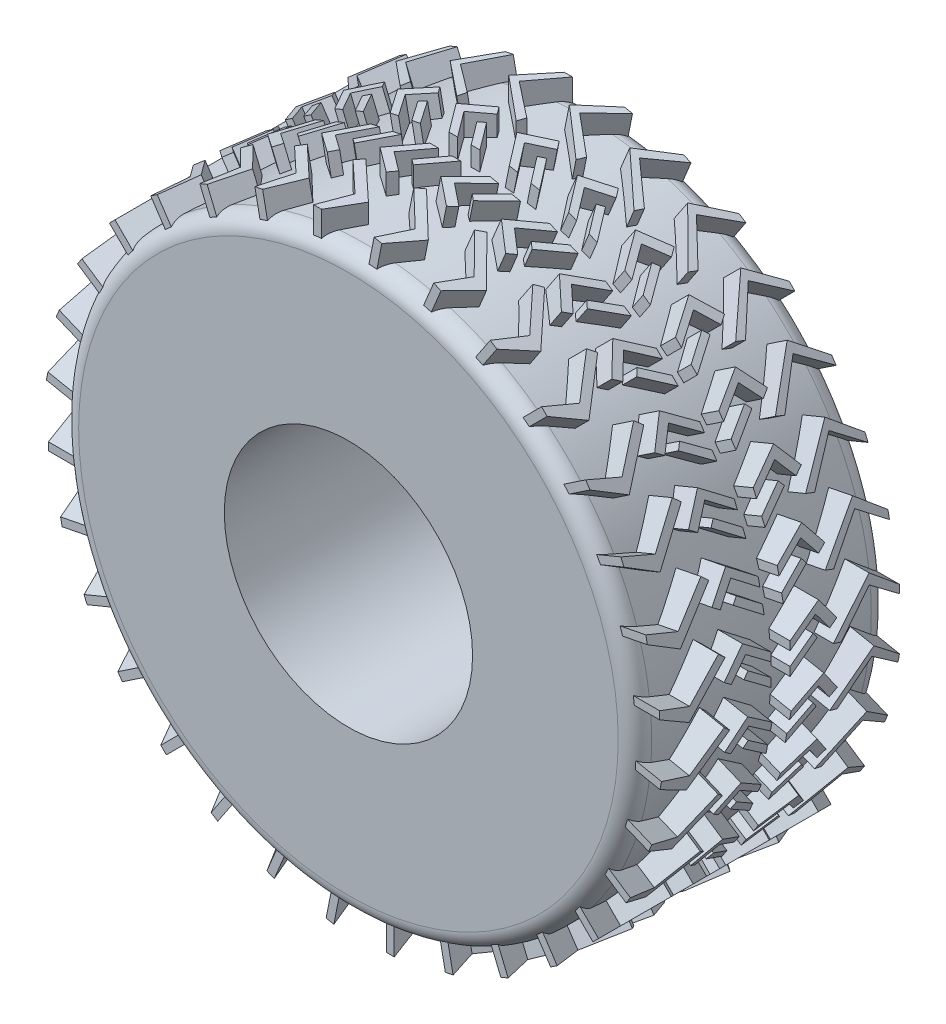
SolidWorks part; units mm, degrees
ref_plane "Front Plane" through (0, 0, 0) normal (0, 0, 1) x (1, 0, 0)
ref_plane "Top Plane" through (0, 0, 0) normal (0, 1, 0) x (1, 0, 0)
ref_plane "Right Plane" through (0, 0, 0) normal (1, 0, 0) x (0, 0, -1)
sketch "Sketch1" plane through (0, 0, 0) normal (0, 0, 1) x (1, 0, 0)
  circle A0 centre (0, 0) radius 60
  circle A1 centre (0, 0) radius 26
  dimension "D1" = 120
  dimension "D2" = 52
extrude "Boss-Extrude2" add sketch "Sketch1" along normal mid plane 53
fillet "Fillet2" radius 3.5 2 edges at (60, 0, -26.5) (60, 0, 26.5)
ref_plane "Plane1" through (0, 64, 0) normal (0, 1, 0) x (1, 0, 0)
sketch "Sketch2" plane through (0, 64, 0) normal (0, 1, 0) x (1, 0, 0)
  line L0 (0, 37.4882) -> (0, -41.0382) construction
  line L1 (-82.5023, 0) -> (94.8564, 0) construction
  line L2 (-7.4291, 2) -> (-7.4291, -2)
  line L3 (-7.4291, 2) -> (-11.9046, 7.9639)
  line L4 (-11.9046, 7.9639) -> (-6.7796, 11.8098)
  line L5 (-6.7796, 11.8098) -> (-5.6519, 10.3069)
  line L6 (-5.6519, 10.3069) -> (-9.6292, 7.3223)
  line L7 (-9.6292, 7.3223) -> (-5.6353, 2)
  line L8 (-5.6353, 2) -> (-7.4291, 2)
  line L13 (-2.7996, 2) -> (-6.4017, 6.8003)
  line L14 (-6.4017, 6.8003) -> (-5.2301, 7.6795)
  line L15 (-5.2301, 7.6795) -> (-0.9682, 2)
  line L16 (-0.9682, 2) -> (-2.7996, 2)
  line L21 (-37.575, -37.5644) -> (33.4067, 33.4172) construction
  line L32 (-6.7796, -25.3397) -> (-3.1767, -19.1352)
  line L33 (-3.1767, -19.1352) -> (-11.2391, -11.6124)
  line L34 (-11.2391, -11.6124) -> (-12.5401, -13.0067)
  line L35 (-12.5401, -13.0067) -> (-6.0701, -19.0437)
  line L36 (-6.0701, -19.0437) -> (-8.4348, -25.3397)
  line L37 (-8.4348, -25.3397) -> (-6.7796, -25.3397)
  line L38 (-0.9682, -2) -> (-2.7996, -2)
  line L39 (-5.2301, -7.6795) -> (-0.9682, -2)
  line L40 (-6.4017, -6.8003) -> (-5.2301, -7.6795)
  line L41 (-2.7996, -2) -> (-6.4017, -6.8003)
  line L42 (-5.6353, -2) -> (-7.4291, -2)
  line L43 (-9.6292, -7.3223) -> (-5.6353, -2)
  line L44 (-5.6519, -10.3069) -> (-9.6292, -7.3223)
  line L45 (-6.7796, -11.8098) -> (-5.6519, -10.3069)
  line L46 (-11.9046, -7.9639) -> (-6.7796, -11.8098)
  line L47 (-7.4291, -2) -> (-11.9046, -7.9639)
  line L48 (-4.5095, 24.9324) -> (-6.2144, 24.9324)
  line L49 (-6.2144, 24.9324) -> (-11.4879, 18.5533)
  line L50 (-11.4879, 18.5533) -> (-2.4273, 11.0631)
  line L51 (-2.4273, 11.0631) -> (-1.8641, 12.7203)
  line L52 (-1.8641, 12.7203) -> (-9.3035, 18.5703)
  line L53 (-9.3035, 18.5703) -> (-4.5095, 24.9324)
  point P8 (-7.4291, 0)
  dimension "D1" = 4
  dimension "D2" = 45
extrude "Boss-Extrude3" add sketch "Sketch2" against normal up to surface (39.8489 mm away) contours L42 L47 L46 L45 L44 L43 | L38 L41 L40 L39 | L16 L15 L14 L13 | L8 L7 L6 L5 L4 L3 | L36 L37 L32 L33 L34 L35 | L52 L53 L48 L49 L50 L51 region at (-6.5322, 64, 2.1164) region at (-9.5737, 64, -5.0518) region at (-3.8289, 64, -4.6261) region at (-7.6072, 64, 25.1735) region at (-3.8289, 64, 4.6261) region at (-7.0414, 64, -21.853) up to face at (26, 0, 26.5)
pattern_circular "CirPattern1" count 32 over 360 about axis through (0, 0, 26.5) along (0, 0, -1) of "Boss-Extrude3"
